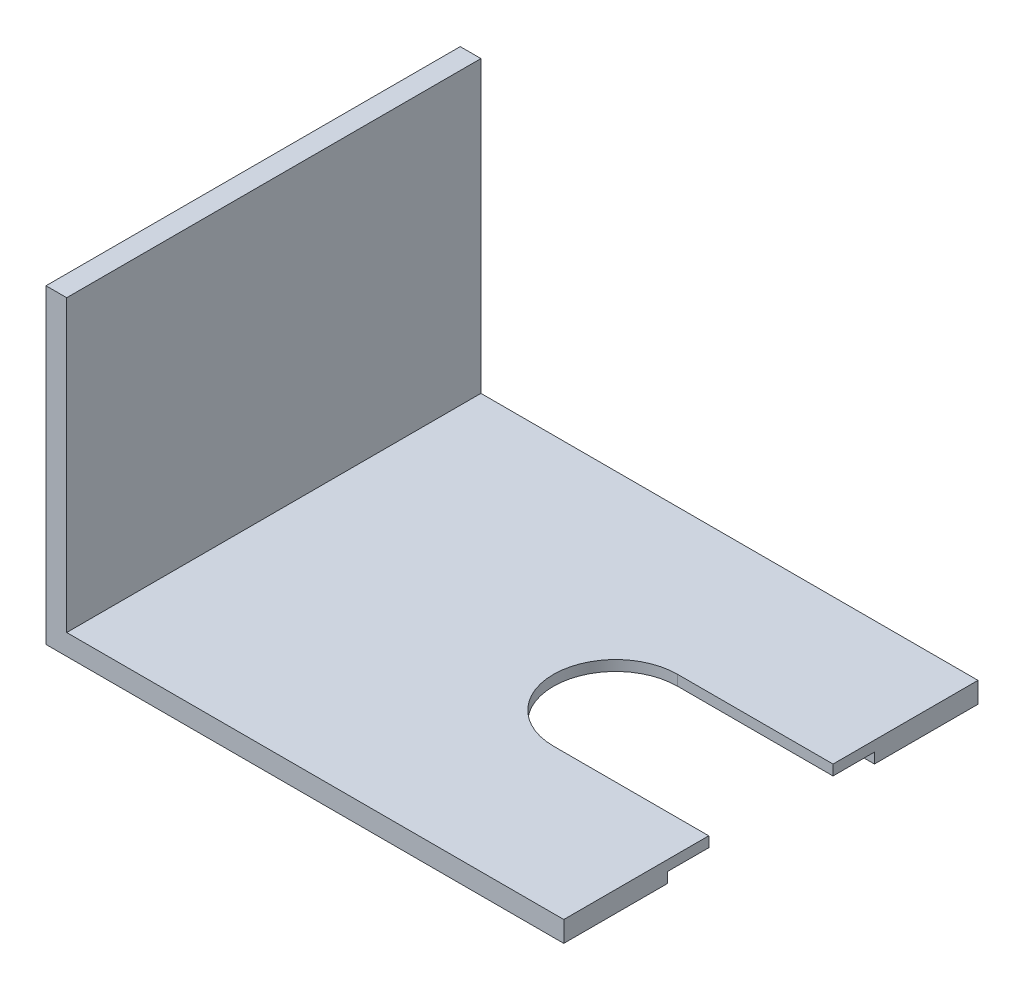
SolidWorks part; units mm, degrees
ref_plane "Front Plane" through (0, 0, 0) normal (0, 0, 1) x (1, 0, 0)
ref_plane "Top Plane" through (0, 0, 0) normal (0, 1, 0) x (1, 0, 0)
ref_plane "Right Plane" through (0, 0, 0) normal (1, 0, 0) x (0, 0, -1)
sketch "Sketch1" plane through (0, 0, 0) normal (0, 0, 1) x (1, 0, 0)
  line L0 (0, 0) -> (0, 30)
  line L1 (0, 30) -> (2, 30)
  line L2 (2, 30) -> (2, 2)
  line L3 (2, 2) -> (50, 2)
  line L4 (50, 2) -> (50, 0)
  line L5 (50, 0) -> (0, 0)
extrude "Boss-Extrude1" add sketch "Sketch1" along normal blind 40
sketch "Sketch4" plane through (0, 0, 0) normal (0, -1, 0) x (-1, 0, 0)
  line L0 (-35, -26) -> (-50, -26)
  line L1 (-50, -40) -> (-50, 0) construction
  line L2 (-35, -14) -> (-50, -14)
  circle A0 centre (-35, -20) radius 6
  line M2 (-50, 0) -> (-50, -40)
extrude "Cut-Extrude1" cut sketch "Sketch4" against normal through all contours A0 L2 L0 M2 | A0 region at (44.769, 0, 20) region at (35, 0, 20)
sketch "Sketch5" plane through (0, 0, 0) normal (0, -1, 0) x (-1, 0, 0)
  line L0 (-35, -30) -> (-50, -30)
  line L1 (-50, -40) -> (-50, -26) construction
  line L2 (-50, -30) -> (-50, -10)
  line L3 (-50, -14) -> (-50, 0) construction
  line L4 (-50, -10) -> (-34.0279, -10.0474)
  circle A0 centre (-35, -20) radius 10
  line M1 (-35, -26) -> (-50, -26)
  line M2 (-50, -26) -> (-50, -40)
  line M6 (-50, 0) -> (-50, -14)
  line M7 (-50, -14) -> (-35, -14)
  arc M8 (-35, -14) -> (-35, -26) centre (-35, -20) cw
extrude "Cut-Extrude2" cut sketch "Sketch5" against normal blind 1 contours A0 L0 M1 M2 | A0 L4 M6 M7 | A0 L4 M1 M7 M8 region at (39.3519, 0, 28.7039) region at (45.1146, 0, 28.2192) region at (45.1534, 0, 11.7953)
